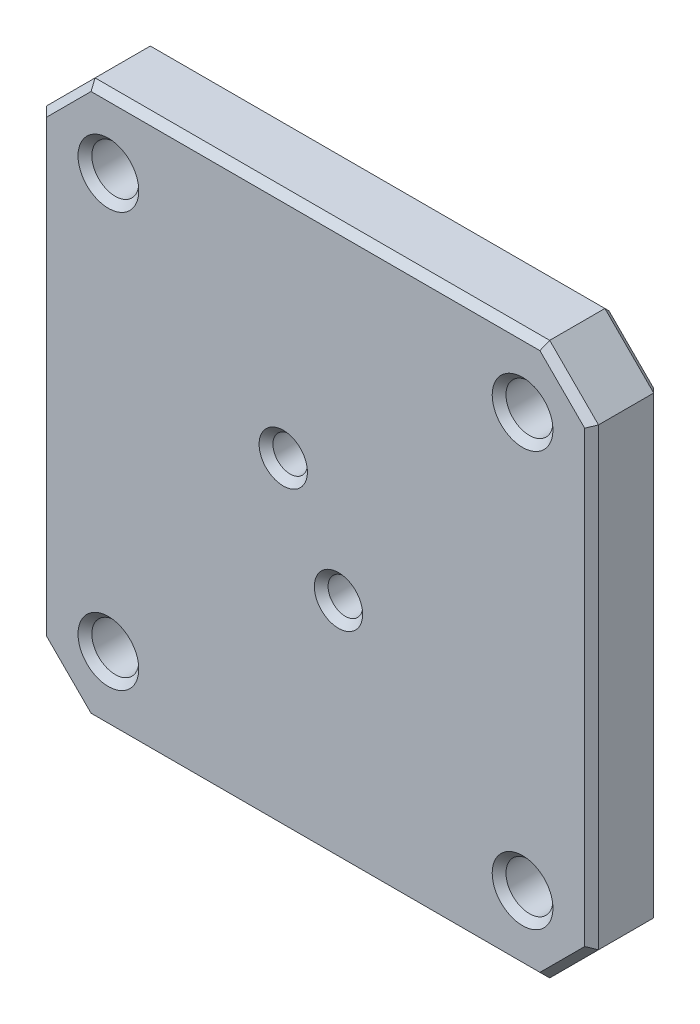
SolidWorks part; units mm, degrees
ref_plane "Top" through (0, 0, 0) normal (0, 0, 1) x (1, 0, 0)
ref_plane "Front" through (0, 0, 0) normal (0, 1, 0) x (1, 0, 0)
ref_plane "Right" through (0, 0, 0) normal (1, 0, 0) x (0, 0, -1)
sketch "Sketch1" plane through (0, 0, 0) normal (0, 0, 1) x (1, 0, 0)
  line L1 (0, 0) -> (40, 0)
  line L2 (0, 0) -> (0, 40)
  line L3 (0, 40) -> (40, 40)
  line L4 (40, 0) -> (40, 40)
  dimension "D1" = 40
  dimension "D2" = 40
extrude "Boss-Extrude1" add sketch "Sketch1" along normal blind 5
sketch "Sketch2" plane through (0, 0, 5) normal (0, 0, 1) x (1, 0, 0)
  line L0 (40, 40) -> (0, 40) construction
  line L1 (5, 35) -> (35, 35) construction
  line L2 (5, 35) -> (5, 5) construction
  line L3 (5, 5) -> (35, 5) construction
  line L4 (35, 35) -> (35, 5) construction
  line L5 (0, 40) -> (0, 0) construction
  circle A0 centre (5, 35) radius 1.7
  circle A1 centre (35, 35) radius 1.7
  circle A2 centre (5, 5) radius 1.7
  circle A3 centre (35, 5) radius 1.7
  dimension "D5" = 3.4
  dimension "D1" = 30
  dimension "D2" = 30
  dimension "D3" = 5
  dimension "D4" = 5
extrude "Cut-Extrude1" cut sketch "Sketch2" against normal blind 5
sketch "Sketch3" plane through (0, 0, 5) normal (0, 0, 1) x (1, 0, 0)
  line L0 (17.6656, 23.4641) -> (21.6656, 16.5359) construction
  line L1 (40, 0) -> (40, 40) construction
  line L3 (40, 40) -> (0, 40) construction
  line L5 (18.9057, 21.3161) -> (25018.9057, -43279.9541) construction
  line L6 (35, 5) -> (29.9944, 2.11) construction
  circle A0 centre (17.6656, 23.4641) radius 1.25
  circle A1 centre (21.6656, 16.5359) radius 1.25
  point P4 (19.6656, 20)
  dimension "D5" = 2.5
  dimension "D1" = 30
  dimension "D2" = 8
  dimension "D3" = 5.78
  dimension "D4" = 20
extrude "Cut-Extrude2" cut sketch "Sketch3" against normal blind 5
chamfer "Chamfer1" distance 3.536 angle 45 4 edges at (0, 40, 2.5) (40, 40, 2.5) (40, 0, 2.5) (0, 0, 2.5)
chamfer "Chamfer2" distance 0.5 angle 45 28 edges at (1.768, 1.768, 0) (20, 0, 0) (38.232, 1.768, 0) (40, 20, 0) (38.232, 38.232, 0) (20, 40, 0) (1.768, 38.232, 0) (0, 20, 0) (6.7, 35, 0) (36.7, 5, 0) (6.7, 5, 0) (36.7, 35, 0) (22.9156, 16.5359, 0) (18.9156, 23.4641, 0) (38.232, 38.232, 5) (40, 20, 5) (38.232, 1.768, 5) (20, 0, 5) (1.768, 1.768, 5) (0, 20, 5) (1.768, 38.232, 5) (20, 40, 5) (6.7, 35, 5) (36.7, 5, 5) (6.7, 5, 5) (36.7, 35, 5) (22.9156, 16.5359, 5) (18.9156, 23.4641, 5)
ref_plane "Plane1" through (22.3269, 12.8904, 0) normal (0.866, 0.5, 0) x (0, 0, -1)
ref_plane "Plane2" through (23.4094, 13.5154, 0) normal (0.866, 0.5, 0) x (0, 0, -1)
